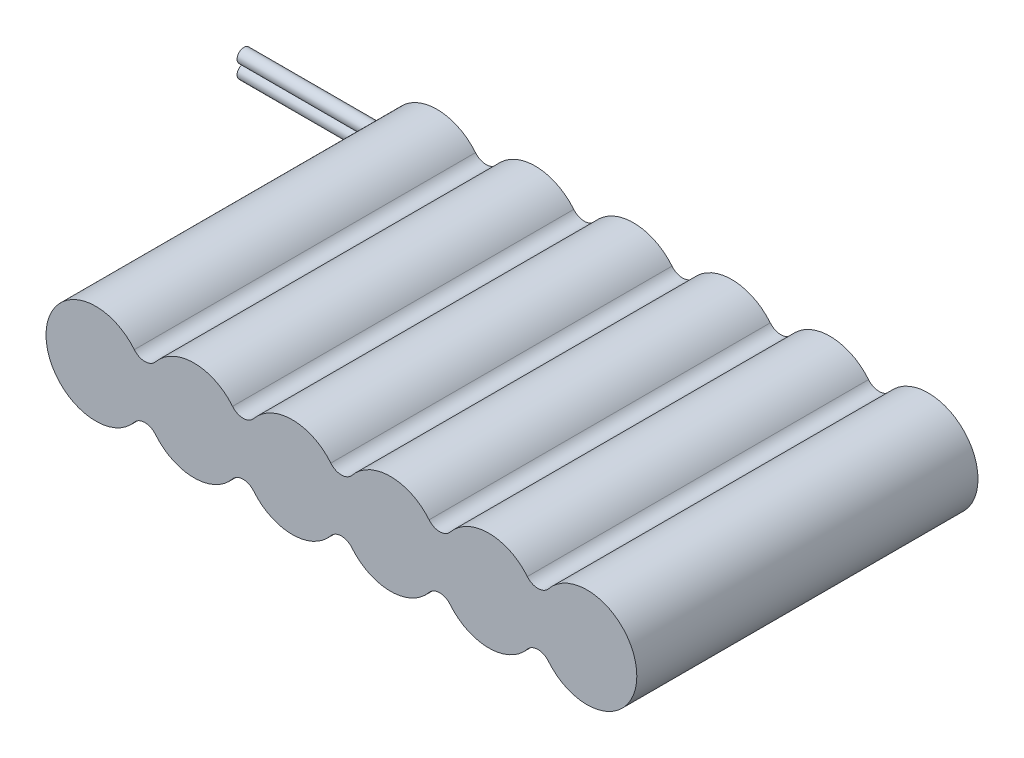
SolidWorks part; units mm, degrees
ref_plane "Front Plane" through (0, 0, 0) normal (0, 0, 1) x (1, 0, 0)
ref_plane "Top Plane" through (0, 0, 0) normal (0, 1, 0) x (1, 0, 0)
ref_plane "Right Plane" through (0, 0, 0) normal (1, 0, 0) x (0, 0, -1)
sketch "Sketch1" plane through (0, 0, 0) normal (0, 0, 1) x (1, 0, 0)
  circle A0 centre (0, 0) radius 9.2604
  circle A1 centre (18.288, 0) radius 9.2604
  circle A2 centre (36.576, 0) radius 9.2604
  circle A3 centre (54.864, 0) radius 9.2604
  circle A4 centre (73.152, 0) radius 9.2604
  circle A5 centre (91.44, 0) radius 9.2604
  circle A12 centre (91.44, 18.288) radius 9.2604 [skipped]
  circle A13 centre (73.152, 18.288) radius 9.2604 [skipped]
  circle A14 centre (54.864, 18.288) radius 9.2604 [skipped]
  circle A15 centre (36.576, 18.288) radius 9.2604 [skipped]
  circle A16 centre (18.288, 18.288) radius 9.2604 [skipped]
  circle A17 centre (0, 18.288) radius 9.2604 [skipped]
  dimension "D1" = 18.5208
  dimension "D2" = 6
  dimension "D3" = 2
extrude "Boss-Extrude4" add sketch "Sketch1" along normal blind 63.5 contours A5 | A4 | A3 | A2 | A1 | A0
fillet "Fillet1" radius 2.54 10 edges at (82.296, -1.4638, 31.75) (64.008, -1.4638, 31.75) (45.72, -1.4638, 31.75) (27.432, -1.4638, 31.75) (9.144, -1.4638, 31.75) (9.144, 1.4638, 31.75) (27.432, 1.4638, 31.75) (45.72, 1.4638, 31.75) (64.008, 1.4638, 31.75) (82.296, 1.4638, 31.75)
ref_plane "Plane1" through (-9.2604, 0, 0) normal (-1, 0, 0) x (0, 0, 1)
sketch "Sketch2" plane through (-9.2604, 0, 0) normal (-1, 0, 0) x (0, 0, 1)
  line L0 (0, 0) -> (10.3182, 0) construction
  line L1 (0, 9.2604) -> (0, -9.2604) construction
  line L4 (1.1204, 0.0088) -> (1.1204, -0.0088)
  line L6 (1.4196, 0.0088) -> (1.4196, -0.0088)
  arc A0 (1.4196, 0.0088) -> (1.1204, 0.0088) centre (1.27, 1.27) ccw
  arc A1 (1.1204, -0.0088) -> (1.4196, -0.0088) centre (1.27, -1.27) ccw
  point P9 (1.27, 0)
extrude "Boss-Extrude5" add sketch "Sketch2" along normal blind 25.4 separate body
ref_plane "Plane2" through (100.7004, 0, 0) normal (1, 0, 0) x (0, 0, -1)
